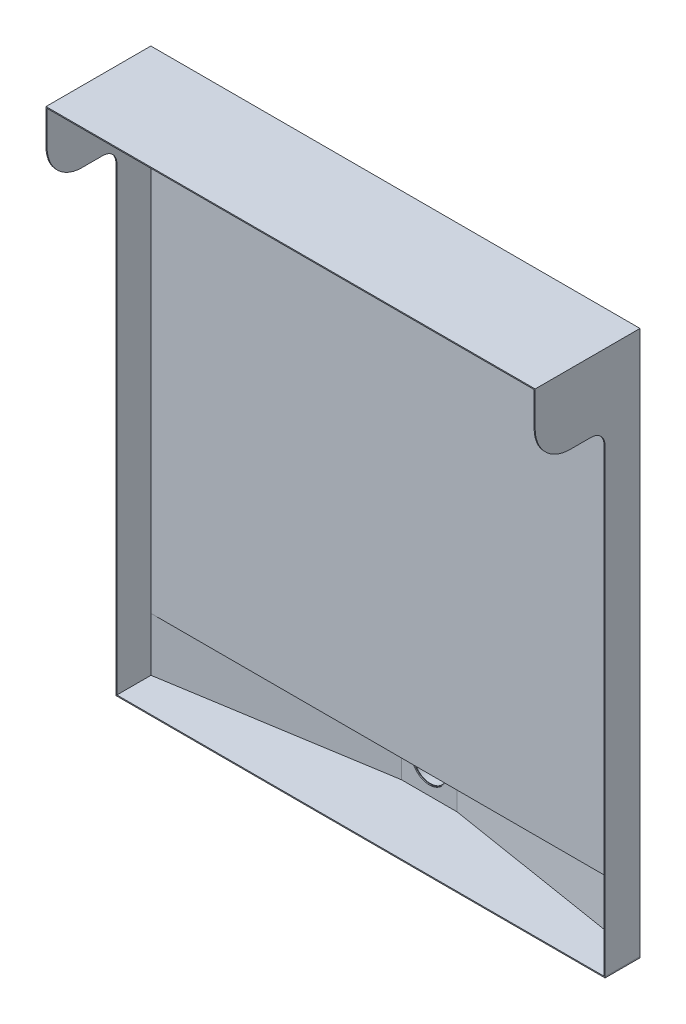
SolidWorks part; units mm, degrees
ref_plane "前视基准面" through (0, 0, 0) normal (0, 0, 1) x (1, 0, 0)
ref_plane "上视基准面" through (0, 0, 0) normal (0, 1, 0) x (1, 0, 0)
ref_plane "右视基准面" through (0, 0, 0) normal (1, 0, 0) x (0, 0, -1)
other "Configuration Table"
sketch "草图6" plane through (0, 0, 0) normal (0, 0, 1) x (1, 0, 0)
  line L1 (350, 390) -> (-350, 390)
  line L2 (350, 390) -> (350, -390)
  line L3 (350, -390) -> (-350, -390)
  line L4 (-350, 390) -> (-350, -390)
  line L5 (350, 390) -> (-350, -390) construction
  line L6 (350, -390) -> (-350, 390) construction
  point P0 (0, 0)
  dimension "D1" = 700
  dimension "D2" = 780
extrude "凸台-拉伸2" add sketch "草图6" along normal blind 150
sketch "草图8" plane through (0, -390, 0) normal (0, -1, 0) x (1, 0, 0)
  line L0 (-350, 0) -> (-40, -50)
  line L3 (40, -50) -> (-40, -50)
  line L5 (0, 0) -> (-40, -50) construction
  line L6 (40, -50) -> (0, 0) construction
  line L7 (40, -50) -> (350, 0)
  line L8 (350, 0) -> (-350, 0)
  point P0 (0, 0)
  dimension "D1" = 50
  dimension "D2" = 80
extrude "凸台-拉伸4" add sketch "草图8" against normal blind 80
shell "抽壳2" thickness 1.5 removed face at (0, 0, 150)
sketch "草图13" plane through (0, 0, -50) normal (0, 0, -1) x (-1, 0, 0)
  line L0 (40, -390) -> (-40, -390) construction
  circle A0 centre (0, -350) radius 25
  point P2 (0.9012, -352.0563)
  point P3 (0, -355.1774)
  point P6 (0, -390)
  dimension "D1" = 50
  dimension "D2" = 40
extrude "切除-拉伸1" cut sketch "草图13" against normal through all contours A0
split "分割5" bodies to split 113 resulting bodies 124 125 split by face at (0, -388.5, 34.2592)
sketch "草图15" plane through (-350, 0, 0) normal (-1, 0, 0) x (0, 0, 1)
  line L0 (150, 390) -> (0, 390) construction
  line L1 (50, 290) -> (250.7911, 290)
  line L2 (50, 290) -> (50, -426.3886)
  line L3 (50, -426.3886) -> (250.7911, -426.3886)
  line L4 (250.7911, 290) -> (250.7911, -426.3886)
  line L5 (0, 390) -> (0, -310) construction
  dimension "D1" = 100
  dimension "D2" = 50
extrude "切除-拉伸2" cut sketch "草图15" against normal through all contours L2 L1 L4 L3
fillet "圆角1" radius 20 2 edges at (-349.25, 290, 50) (349.25, 290, 50)
fillet "圆角2" radius 50 2 edges at (349.25, 290, 150) (-349.25, 290, 150)
sketch "草图16" plane through (0, 0, -50) normal (0, 0, -1) x (-1, 0, 0)
  line L1 (40, -390) -> (-40, -390) construction
  circle A3 centre (0, -350) radius 25
  circle A4 centre (0, -350) radius 24
  point P2 (-0.4012, -331.1238)
  point P4 (-2.1626, -355.0116)
  point P5 (0, -355.2226)
  dimension "D1" = 50
  dimension "D2" = 48
  dimension "D3" = 40
extrude "凸台-拉伸5" add sketch "草图16" along normal blind 25 separate body
sketch "折弯-线28" [suppressed] plane through (0, 0, 0) normal (0, 1, 0) x (1, 0, 0)
sketch "边界框28" [suppressed] plane through (0, 0, 0) normal (0, 1, 0) x (1, 0, 0)
